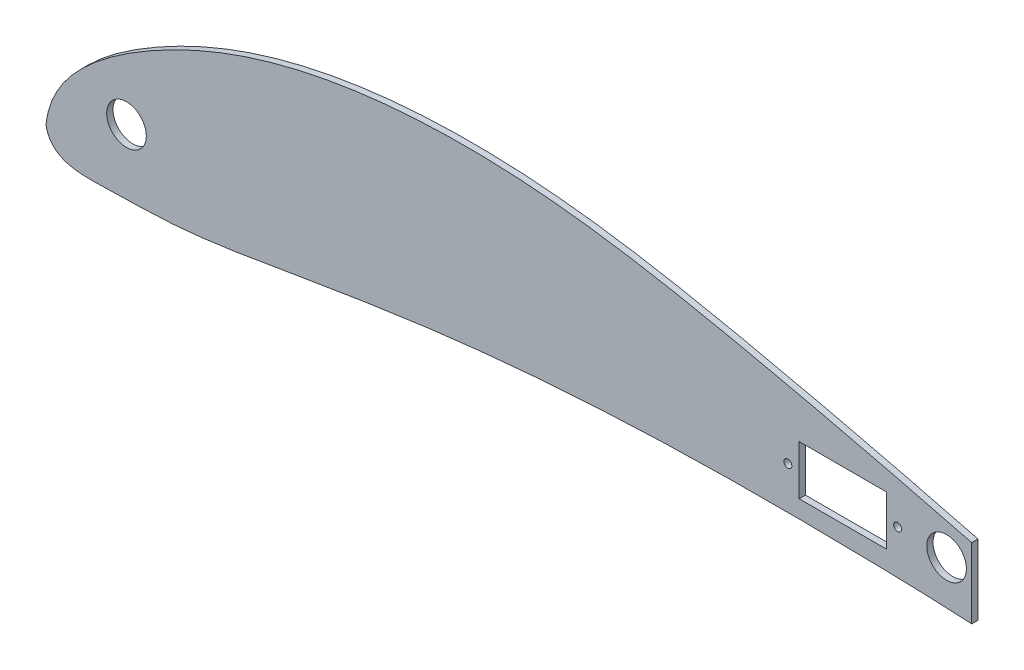
SolidWorks part; units mm, degrees
material "Balsa"
ref_plane "Front Plane" through (0, 0, 0) normal (0, 0, 1) x (1, 0, 0)
ref_plane "Top Plane" through (0, 0, 0) normal (0, 1, 0) x (1, 0, 0)
ref_plane "Right Plane" through (0, 0, 0) normal (1, 0, 0) x (0, 0, -1)
sketch "Sketch1" plane through (0, 0, 0) normal (0, 0, 1) x (1, 0, 0)
  spline S0 degree 3 poles (0.0006, 0.0001) (0.8106, 7.3592) (8.6491, 17.8566) (26.2867, 29.9752) (52.1111, 42.0692) (89.5976, 49.2908) (131.4008, 47.8848) (173.2567, 40.0411) (217.9611, 29.613) (256.9521, 19.5289) (290.3598, 8.711) (301.2732, 4.3828) (314.8169, -0.5162) (309.8463, 0.0001) knots 0 0 0 0 0.060864 0.113688 0.188609 0.312909 0.448482 0.557612 0.691544 0.852438 0.929756 0.976058 1 1 1 1
  spline S1 degree 3 poles (309.8463, 0.0001) (303.9568, 1.471) (293.9895, 2.094) (276.264, 4.5144) (260.8463, 5.4274) (235.8588, 7.8703) (205.1014, 8.8381) (157.7186, 9.0307) (110.4973, 6.1815) (66.5062, -0.5867) (36.4547, -6.0985) (15.3166, -6.1891) (1.2307, -6.9241) (0.0006, 0.0001) knots 0 0 0 0 0.057787 0.095275 0.171021 0.205339 0.335319 0.464904 0.658702 0.785512 0.893517 0.943092 1 1 1 1
extrude "Boss-Extrude1" add sketch "Sketch1" along normal blind 1.5875
sketch "Sketch2" plane through (0, 0, 1.5875) normal (0, 0, 1) x (1, 0, 0)
  circle A0 centre (20.32, 10.16) radius 5
  circle A1 centre (227.2963, 19.0501) radius 5
  dimension "D2" = 10
  dimension "D3" = 10
  dimension "D6" = 20.32
  dimension "D1" = 82.55
  dimension "D4" = 19.05
  dimension "D5" = 10.16
extrude "Cut-Extrude1" cut sketch "Sketch2" against normal through all
sketch "Sketch3" plane through (0, 0, 1.5875) normal (0, 0, 1) x (1, 0, 0)
  line L1 (350.4863, -6.3499) -> (233.6463, -6.3499)
  line L2 (350.4863, -6.3499) -> (350.4863, 44.4501)
  line L3 (350.4863, 44.4501) -> (233.6463, 44.4501)
  line L4 (233.6463, -6.3499) -> (233.6463, 44.4501)
  circle A0 centre (227.2963, 19.0501) radius 5 construction
  dimension "D1" = 6.35
  dimension "D2" = 116.84
  dimension "D3" = 50.8
  dimension "D4" = 44.45
extrude "Cut-Extrude2" cut sketch "Sketch3" against normal through all contours L3 L4 L1 L2
sketch "Sketch4" plane through (0, 0, 1.5875) normal (0, 0, 1) x (1, 0, 0)
  line L0 (190.0992, 19.5181) -> (187.2492, 19.5181) construction
  line L1 (190.0992, 25.7681) -> (212.0992, 25.7681)
  line L2 (190.0992, 25.7681) -> (190.0992, 13.2681)
  line L3 (190.0992, 13.2681) -> (212.0992, 13.2681)
  line L4 (212.0992, 25.7681) -> (212.0992, 13.2681)
  line L5 (212.0992, 19.5181) -> (214.9492, 19.5181) construction
  circle A0 centre (214.9492, 19.5181) radius 1.0008
  circle A1 centre (187.2492, 19.5181) radius 1.0008
  dimension "D4" = 2.0015
  dimension "D1" = 2.85
  dimension "D2" = 22
  dimension "D3" = 12.5
extrude "Cut-Extrude3" cut sketch "Sketch4" against normal through all
